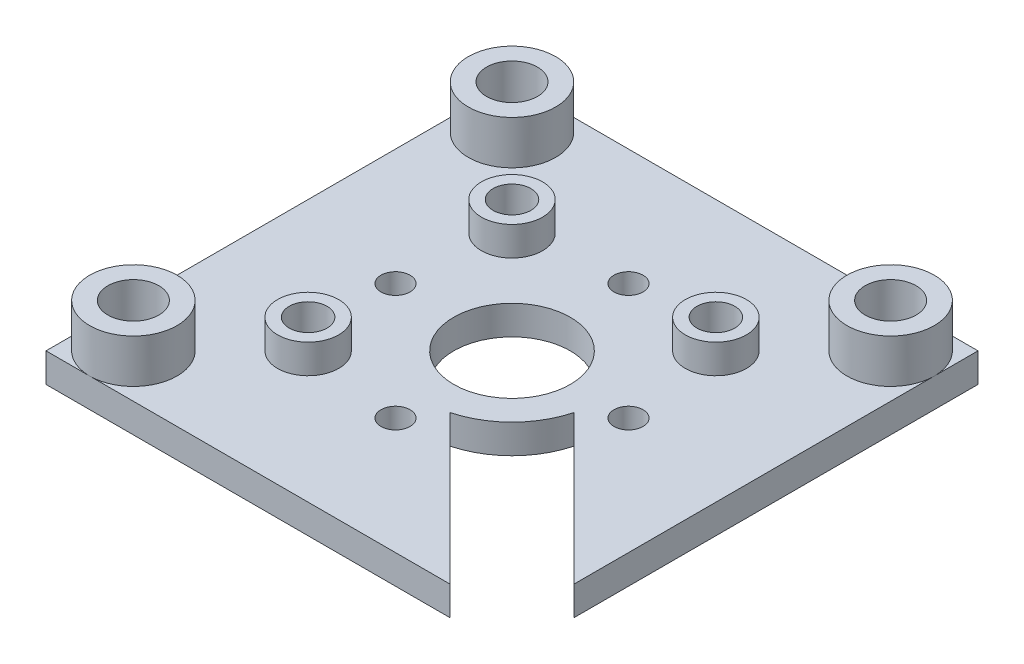
SolidWorks part; units mm, degrees
ref_plane "前视基准面" through (0, 0, 0) normal (0, 0, 1) x (1, 0, 0)
ref_plane "上视基准面" through (0, 0, 0) normal (0, 1, 0) x (1, 0, 0)
ref_plane "右视基准面" through (0, 0, 0) normal (1, 0, 0) x (0, 0, -1)
sketch "草图1" plane through (0, 0, 0) normal (0, 1, 0) x (1, 0, 0)
  line L0 (0, 0) -> (8, 0) construction
  line L1 (0, 0) -> (0, 8) construction
  line L3 (-16, 16) -> (16, 16)
  line L4 (-16, 16) -> (-16, -16)
  line L5 (-16, -16) -> (16, -16)
  line L6 (16, 16) -> (16, -16)
  circle A0 centre (0, 0) radius 8 construction
  circle A1 centre (8, 0) radius 1
  circle A2 centre (0, -8) radius 1
  circle A3 centre (-8, 0) radius 1
  circle A4 centre (0, 8) radius 1
  circle A5 centre (0, 0) radius 4
  circle A6 centre (0, 0) radius 16 construction
  circle A7 centre (13, 13) radius 1.75
  circle A8 centre (-13, 13) radius 1.75
  circle A9 centre (13, -13) radius 1.75
  circle A10 centre (-13, -13) radius 1.75
  dimension "D1" = 16
  dimension "D2" = 2
  dimension "D4" = 8
  dimension "D5" = 32
  dimension "D6" = 3.5
  dimension "D7" = 26
  dimension "D8" = 26
  dimension "D3" = 4
extrude "凸台-拉伸1" add sketch "草图1" along normal blind 2 contours L6 L3 L4 L5 A10 A8 A7 A5 A4 A3 A2 A1 A9 region at (0, 0, -15.5475)
sketch "草图2" plane through (0, 2, 0) normal (0, 1, 0) x (1, 0, 0)
  line L0 (0, 0) -> (7, 7) construction
  line L1 (0, 0) -> (9.8995, 0) construction
  line L2 (5.7956, -1.5529) -> (16, -11.7574)
  line L3 (16, 16) -> (16, -16) construction
  line L4 (0, 0) -> (16, -16) construction
  line L5 (1.5529, -5.7956) -> (11.7574, -16)
  line L6 (16, -11.7574) -> (16, -16)
  line L7 (16, -16) -> (11.7574, -16)
  circle A0 centre (0, 0) radius 9.8995 construction
  circle A1 centre (7, 7) radius 1.3
  circle A2 centre (7, 7) radius 2.1
  circle A3 centre (7, -7) radius 2.1
  circle A4 centre (7, -7) radius 1.3
  circle A5 centre (-7, -7) radius 2.1
  circle A6 centre (-7, -7) radius 1.3
  circle A7 centre (-7, 7) radius 2.1
  circle A8 centre (-7, 7) radius 1.3
  circle A9 centre (0, 0) radius 6 construction
  arc A10 (5.7956, -1.5529) -> (1.5529, -5.7956) centre (0, 0) cw
  line M20 (16, -16) -> (16, 16)
  line M23 (-16, -16) -> (16, -16)
  circle M24 centre (13, -13) radius 1.75
  dimension "D1" = 2.6
  dimension "D2" = 4.2
  dimension "D6" = 12
  dimension "D4" = 45
  dimension "D5" = 14
  dimension "D7" = 6
  dimension "D3" = 4
extrude "凸台-拉伸3" add sketch "草图2" along normal blind 2 contours A5 A6 | A7 A8 | A2 A1 region at (4.9594, 2, -7) region at (-9.0406, 2, 7) region at (-9.0406, 2, -7)
extrude "切除-拉伸2" cut sketch "草图2<6>" against normal up to surface (2 mm away) contours A8 | A6 | A1 | A3 A4 | A4 | L2 A10 L5 A3 M23 M20 M24 region at (9.5339, 2, 9.5339) region at (7, 2, -7) region at (4.9594, 2, 7) region at (7, 2, 7) region at (-7, 2, 7) region at (-7, 2, -7) up to face at (-13, 0, 14.75)
sketch "草图2<6>" plane through (0, 2, 0) normal (0, 1, 0) x (1, 0, 0) same geometry as "草图2"
sketch "草图3" plane through (0, 0, 0) normal (0, -1, 0) x (1, 0, 0)
  line L0 (0, 0) -> (3.1022, 0) construction
  line L1 (0, 0) -> (0, 3.2085) construction
  circle A0 centre (-13, 13) radius 1.75
  circle A1 centre (-13, 13) radius 3
  circle A2 centre (-13, 13) radius 1.75 construction
  circle A3 centre (-13, -13) radius 1.75
  circle A4 centre (-13, -13) radius 3
  circle A5 centre (13, -13) radius 1.75
  circle A6 centre (13, -13) radius 3
  dimension "D1" = 3.5
  dimension "D2" = 6
extrude "凸台-拉伸5" add sketch "草图3" against normal blind 5
